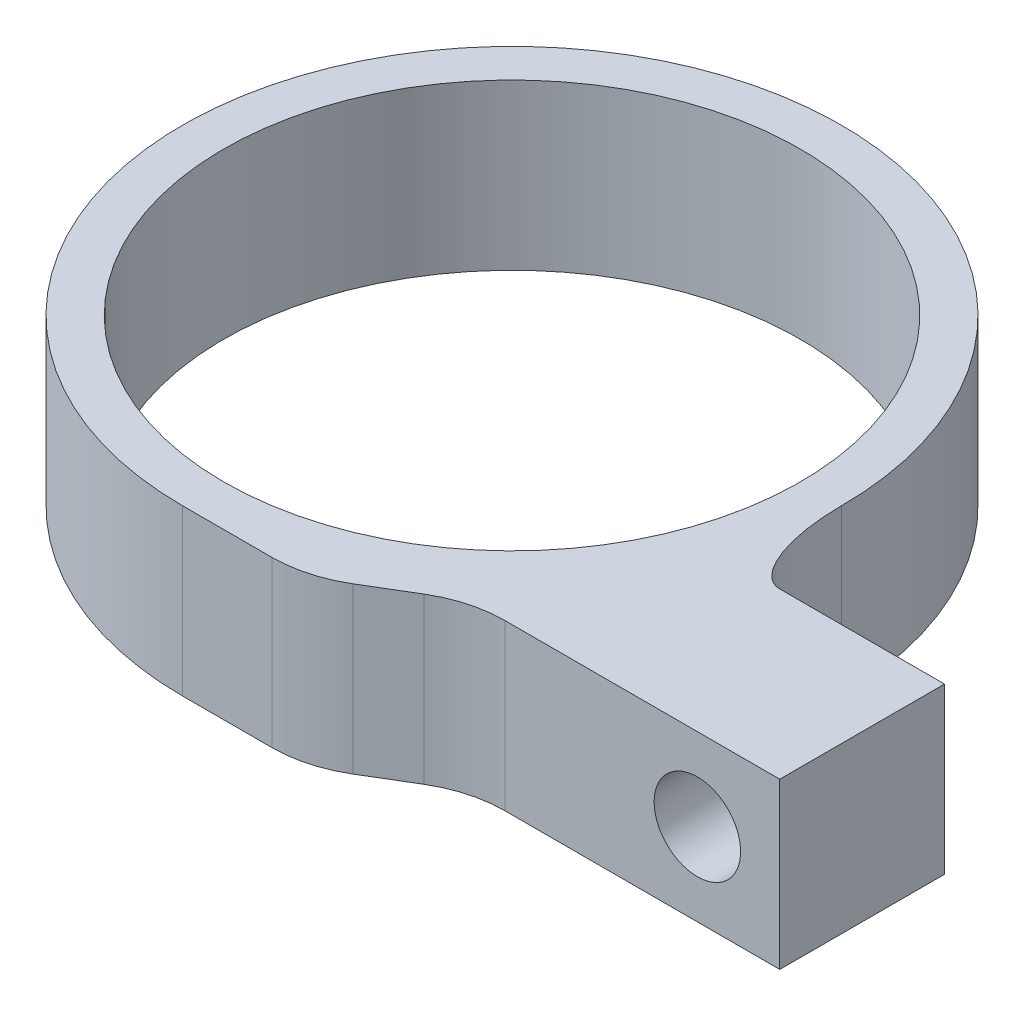
SolidWorks part; units mm, degrees
material "Rubber"
ref_plane "Front Plane" through (0, 0, 0) normal (0, 0, 1) x (1, 0, 0)
ref_plane "Top Plane" through (0, 0, 0) normal (0, 1, 0) x (1, 0, 0)
ref_plane "Right Plane" through (0, 0, 0) normal (1, 0, 0) x (0, 0, -1)
sketch "Sketch1" plane through (0, 0, 0) normal (0, 1, 0) x (1, 0, 0)
  line L0 (0, -16) -> (6, -16)
  line L1 (6, -16) -> (11, -13)
  line L2 (11, -13) -> (26, -13)
  line L3 (26, -13) -> (26, -5)
  line L4 (26, -5) -> (16, -5)
  line L5 (16, -5) -> (16, 0)
  circle A0 centre (0, 0) radius 14
  arc A1 (16, 0) -> (0, -16) centre (0, 0) ccw
  dimension "D1" = 16
  dimension "D2" = 28
  dimension "D3" = 6
  dimension "D4" = 3
  dimension "D5" = 5
  dimension "D6" = 8
  dimension "D7" = 10
extrude "Boss-Extrude1" add sketch "Sketch1" along normal blind 8
fillet "Fillet2" radius 6 2 edges at (11, 4, 13) (6, 4, 16)
sketch "Sketch2" plane through (0, 0, 5) normal (0, 0, -1) x (-1, 0, 0)
  line L0 (-26, 8) -> (-26, 0) construction
  circle A0 centre (-22, 4) radius 2.1
  dimension "D1" = 4.2
  dimension "D2" = 4
extrude "Cut-Extrude1" cut sketch "Sketch2" against normal through all
fillet "Fillet3" radius 2 1 edges at (16, 4, 5) second distance 5 first distance on face at (19.9, 4, 5)
